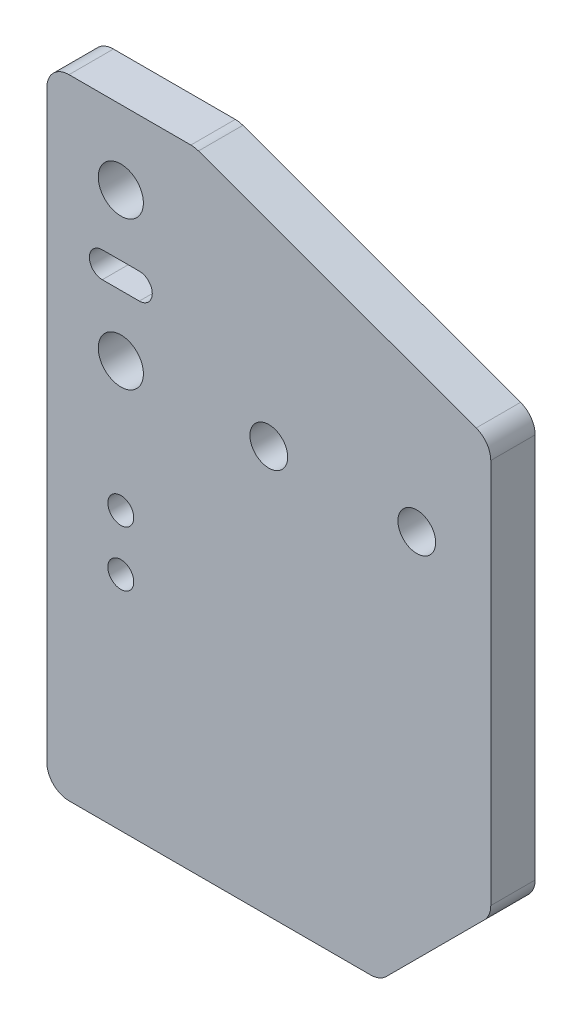
SolidWorks part; units mm, degrees
material "Acrylic (Medium-high impact)"
ref_plane "Спереди" through (0, 0, 0) normal (0, 0, 1) x (1, 0, 0)
ref_plane "Сверху" through (0, 0, 0) normal (0, 1, 0) x (1, 0, 0)
ref_plane "Справа" through (0, 0, 0) normal (1, 0, 0) x (0, 0, -1)
sketch "Model" plane through (0, 0, 0) normal (0, 0, 1) x (1, 0, 0)
  line L0 (59.1213, 14.1213) -> (45.8787, 0.8787)
  line L2 (5.4335, 55) -> (15.2657, 55) construction
  line L3 (5.6697, 75) -> (14.2485, 75) construction
  line L4 (10, 75) -> (10, 55) construction
  line L5 (12.5, 65) -> (7.5, 65) construction
  line L6 (12.5, 63.25) -> (7.5, 63.25)
  line L7 (12.5, 66.75) -> (7.5, 66.75)
  line L12 (3, 0) -> (43.7574, 0)
  line L13 (60, 16.2426) -> (60, 68.3406)
  line L14 (58.0261, 71.1596) -> (20.4971, 84.8191)
  line L8721 (3, 85) -> (19.471, 85)
  line L8759 (0, 3) -> (0, 82)
  arc A0 (58.0261, 71.1596) -> (60, 68.3406) centre (57, 68.3406) cw
  arc A1 (20.4971, 84.8191) -> (19.471, 85) centre (19.471, 82) ccw
  arc A2 (60, 16.2426) -> (59.1213, 14.1213) centre (57, 16.2426) cw
  circle A3 centre (10, 75) radius 3.05
  circle A4 centre (10, 55) radius 3.05
  arc A5 (0, 82) -> (3, 85) centre (3, 82) cw
  arc A6 (0, 3) -> (3, 0) centre (3, 3) ccw
  arc A7 (45.8787, 0.8787) -> (43.7574, 0) centre (43.7574, 3) cw
  arc A8 (12.5, 63.25) -> (12.5, 66.75) centre (12.5, 65) ccw
  arc A9 (7.5, 66.75) -> (7.5, 63.25) centre (7.5, 65) ccw
  circle A11 centre (30, 55) radius 2.55
  circle A12 centre (50, 55) radius 2.55
  point P17 (20, 85)
  point P30 (0, 85)
  point P32 (45, 0)
  point P33 (0, 0)
  point P35 (20, 85)
  point P37 (10, 65)
  dimension "D16" = 6.1
  dimension "D18" = 45
  dimension "D19" = 3
  dimension "D28" = 5.1
  dimension "D6" = 60
  dimension "D13" = 5
  dimension "D4" = 85
  dimension "D5" = 10
  dimension "D7" = 20
  dimension "D8" = 10
  dimension "D9" = 70
  dimension "D10" = 10
  dimension "D11" = 3.5
  dimension "D12" = 20
  dimension "D15" = 45
  dimension "D30" = 20
  dimension "D31" = 20
extrude "Body" add sketch "Model" along normal blind 6
sketch "Sketch1" plane through (0, 0, 0) normal (0, 0, -1) x (-1, 0, 0)
  line L0 (-10, 43.645) -> (-10, 21.6609) construction
  line L3 (0, 82) -> (0, 3) construction
  line L4 (-3, 0) -> (-43.7574, 0) construction
  circle A0 centre (-10, 30) radius 1.75
  circle A1 centre (-10, 37.5) radius 1.75
  dimension "D1" = 3.5
  dimension "D3" = 7.5
  dimension "D4" = 30
  dimension "D5" = 10
extrude "ForSensor" cut sketch "Sketch1" against normal blind 10 contours A0 | A1
sketch "Sketch2" [suppressed] plane through (0, 0, 6) normal (0, 0, 1) x (1, 0, 0)
  line L0 (60, 16.2426) -> (60, 68.3406) construction
  line L1 (3, 0) -> (43.7574, 0) construction
  circle A0 centre (40, 26) radius 11
  dimension "D1" = 22
  dimension "D2" = 20
  dimension "D3" = 26
extrude "CableIHoleInput" [suppressed] cut sketch "Sketch2" against normal through all
sketch "Sketch3" [suppressed] plane through (0, 0, 6) normal (0, 0, 1) x (1, 0, 0)
  line L0 (0, 82) -> (0, 3) construction
  line L1 (3, 0) -> (43.7574, 0) construction
  circle A0 centre (6.5, 30) radius 1.75
  circle A1 centre (6.5, 21) radius 1.75
  dimension "D2" = 3.5
  dimension "D1" = 6.5
  dimension "D3" = 9
  dimension "D4" = 20
extrude "CableMount" [suppressed] cut sketch "Sketch3" against normal through all
